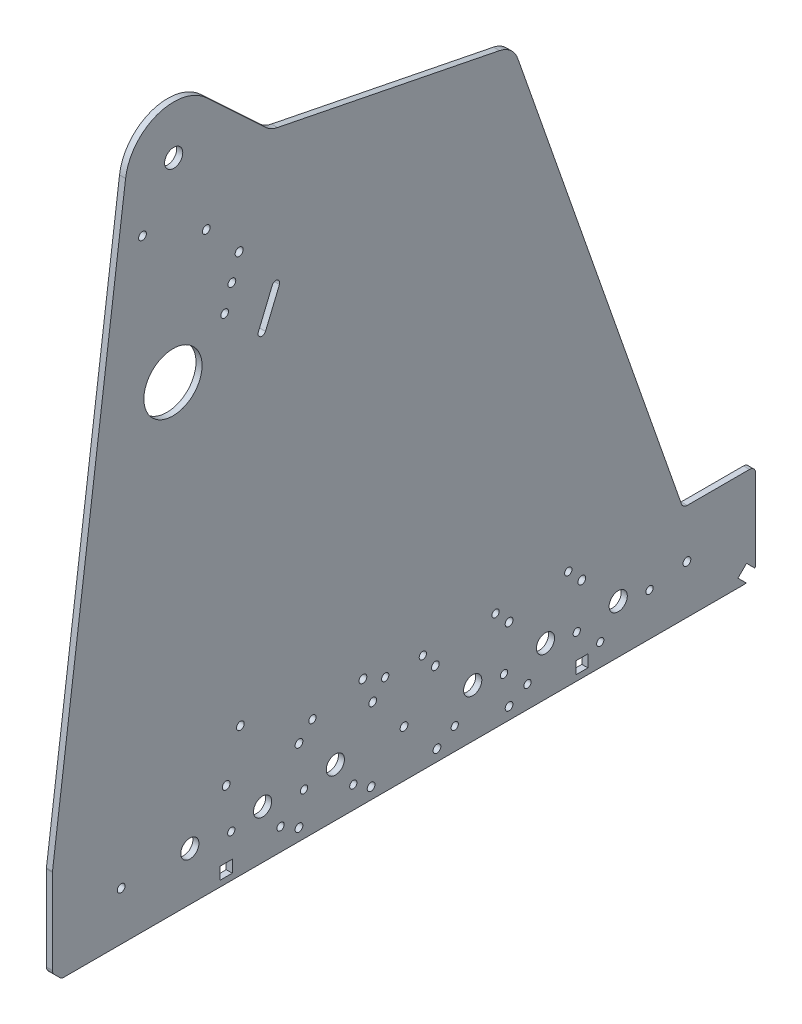
SolidWorks part; units mm, degrees
ref_plane "Front Plane" through (0, 0, 0) normal (0, 0, 1) x (1, 0, 0)
ref_plane "Top Plane" through (0, 0, 0) normal (0, 1, 0) x (1, 0, 0)
ref_plane "Right Plane" through (0, 0, 0) normal (1, 0, 0) x (0, 0, -1)
sketch "Sketch1" plane through (0, 0, 0) normal (1, 0, 0) x (0, 0, -1)
  line L0 (-184.15, -24.6062) -> (184.15, -24.6062)
  line L1 (184.15, -24.6062) -> (184.15, 26.1938)
  line L2 (184.15, 26.1938) -> (146.05, 26.1937)
  line L3 (146.05, 26.1937) -> (57.15, 280.1938)
  line L5 (-145.839, 321.5609) -> (-184.15, 26.1938)
  line L6 (-184.15, 26.1938) -> (-184.15, -24.6062)
  line L7 (-184.15, 350.0437) -> (184.15, 350.0437) construction
  line L8 (57.15, 280.1938) -> (-69.85, 305.5938)
  line L9 (-69.85, 305.5938) -> (-103.3099, 336.854)
  arc A0 (-103.3099, 336.854) -> (-145.839, 321.5609) centre (-120.65, 318.2937) ccw
  point P8 (0, -24.6062)
  dimension "D1" = 368.3
  dimension "D7" = 25.4
  dimension "D2" = 50.8
  dimension "D3" = 38.1
  dimension "D4" = 24.6062
  dimension "D5" = 374.65
  dimension "D6" = 304.8
  dimension "D8" = 342.9
  dimension "D9" = 127
  dimension "D10" = 304.8
  dimension "D11" = 25.4
  dimension "D12" = 127
extrude "Boss-Extrude1" add sketch "Sketch1" along normal blind 3.175
chamfer "Chamfer1" distance 4.7625 angle 45 2 edges at (1.5875, -24.6062, 184.15) (1.5875, -24.6062, -184.15)
fillet "Fillet1" radius 12.7 2 edges at (1.5875, 305.5938, 69.85) (1.5875, 280.1938, -57.15)
fillet "Fillet2" radius 3.175 3 edges at (1.5875, 26.1938, 184.15) (1.5875, 26.1938, -184.15) (1.5875, 26.1937, -146.05)
fillet "Fillet3" radius 3.175 4 edges at (1.5875, -19.8438, -184.15) (1.5875, -24.6062, -179.3875) (1.5875, -19.8437, 184.15) (1.5875, -24.6062, 179.3875)
sketch "Sketch16" plane through (3.175, 0, 0) normal (1, 0, 0) x (0, 0, -1)
  circle A0 centre (112.1746, 0.7937) radius 4.7625
  circle A1 centre (74.0746, 0.7937) radius 4.7625
  circle A2 centre (35.9746, 0.7937) radius 4.7625
  circle A3 centre (-35.9746, 0.7938) radius 4.7625
  circle A4 centre (-74.0746, 0.7938) radius 4.7625
  circle A5 centre (-112.1746, 0.7937) radius 4.7625
  dimension "D1" = 9.525
  dimension "D2" = 9.525
extrude "Cut-Extrude1" cut sketch "Sketch16" against normal up to next
sketch "Sketch25" plane through (3.175, 0, 0) normal (1, 0, 0) x (0, 0, -1)
  circle A0 centre (102.7672, -13.0003) radius 1.905 construction
  circle A1 centre (86.0486, 27.3622) radius 1.905 construction
  circle A2 centre (128.5804, -2.3081) radius 1.905 construction
  circle A3 centre (102.7672, -13.0003) radius 1.905
  circle A4 centre (86.0486, 27.3622) radius 1.905
  circle A5 centre (128.5804, -2.3081) radius 1.905
  circle A6 centre (64.6672, -13.0003) radius 1.905 construction
  circle A8 centre (-9.8486, 27.3622) radius 1.905 construction
  circle A10 centre (-47.9486, 27.3622) radius 1.905 construction
  circle A11 centre (-90.4804, -2.3081) radius 1.905 construction
  circle A12 centre (-64.6672, -13.0003) radius 1.905 construction
  circle A14 centre (-52.3804, -2.3081) radius 1.905 construction
  circle A15 centre (-26.5672, -13.0003) radius 1.905 construction
  circle A16 centre (9.8486, 27.3622) radius 1.905 construction
  circle A17 centre (26.5672, -13.0003) radius 1.905 construction
  circle A18 centre (47.9486, 27.3622) radius 1.905 construction
  circle A19 centre (52.3804, -2.3081) radius 1.905 construction
  circle A20 centre (90.4804, -2.3081) radius 1.905 construction
  circle A21 centre (-9.8486, 27.3622) radius 1.905
  circle A23 centre (-47.9486, 27.3622) radius 1.905
  circle A24 centre (-90.4804, -2.3081) radius 1.905
  circle A25 centre (-64.6672, -13.0003) radius 1.905
  circle A27 centre (-52.3804, -2.3081) radius 1.905
  circle A28 centre (-26.5672, -13.0003) radius 1.905
  circle A29 centre (9.8486, 27.3622) radius 1.905
  circle A30 centre (26.5672, -13.0003) radius 1.905
  circle A31 centre (47.9486, 27.3622) radius 1.905
  circle A32 centre (64.6672, -13.0003) radius 1.905
  circle A33 centre (52.3804, -2.3081) radius 1.905
  circle A34 centre (90.4804, -2.3081) radius 1.905
extrude "Cut-Extrude4" cut sketch "Sketch25" against normal up to next
sketch "Sketch23" plane through (3.175, 0, 0) normal (1, 0, 0) x (0, 0, -1)
  point P0 (-55.0246, -18.3223)
  point P3 (-55.0246, 19.9098)
  point P6 (-93.1246, 19.9098)
  point P9 (-17.2515, -18.6426)
  point P12 (-16.4124, 19.3854)
  point P15 (16.4124, 19.3854)
  point P18 (17.2515, -18.6426)
  point P21 (55.0246, -18.3223)
  point P27 (93.1246, 19.9098)
  point P30 (55.0246, 19.9098)
hole_wizard "#8 (0.16) Diameter Hole1" positions "Sketch23" profile "Sketch24" hole size "#8" standard "ANSI Inch" end condition up to next
sketch "Sketch24" plane through (3.175, -18.3223, 55.0246) normal (0, 1, 0) x (0, 0, -1)
  line L0 (0, 0) -> (0, 3.175)
  line L1 (0, 3.175) -> (2.032, 3.175)
  line L2 (2.032, 3.175) -> (2.032, 0)
  line L5 (2.032, 0) -> (0, 0)
  line L11 (0, -6.35) -> (0, 107.95) construction
  dimension "Thru Hole Dia." = 4.064
  dimension "Thru Hole Depth" = 3.175
sketch "Sketch22" plane through (3.175, 0, 0) normal (1, 0, 0) x (0, 0, -1)
  line L0 (-96.2996, -15.1473) -> (-89.9496, -15.1473) construction
  line L1 (-96.2996, -15.1473) -> (-89.9496, -15.1473)
  line L2 (-96.2996, -15.1473) -> (-96.2996, -21.4973)
  line L3 (-96.2996, -21.4973) -> (-89.9496, -21.4973)
  line L4 (-89.9496, -15.1473) -> (-89.9496, -21.4973)
  line L5 (-96.2996, -15.1473) -> (-89.9496, -21.4973) construction
  line L6 (-96.2996, -21.4973) -> (-89.9496, -15.1473) construction
  line L7 (-89.9496, -15.1473) -> (-89.9496, -19.8734) construction
  line L77 (179.3875, -24.6062) -> (183.8776, -20.1161)
  line L78 (179.3875, -24.6062) -> (174.8974, -20.1161)
  line L79 (183.8776, -20.1161) -> (179.3875, -15.626)
  line L80 (174.8974, -20.1161) -> (179.3875, -15.626)
  line L81 (180.3174, -23.6763) -> (183.2201, -20.7737) construction
  line L82 (-178.0724, -24.6062) -> (178.0724, -24.6062) construction
  line L84 (89.9496, -21.4973) -> (96.2996, -21.4973)
  line L85 (89.9496, -21.4973) -> (89.9496, -15.1473)
  line L86 (89.9496, -15.1473) -> (96.2996, -15.1473)
  line L87 (96.2996, -21.4973) -> (96.2996, -15.1473)
  line L88 (89.9496, -21.4973) -> (96.2996, -15.1473) construction
  line L89 (89.9496, -15.1473) -> (96.2996, -21.4973) construction
  point P0 (-93.1246, -18.3223)
  point P19 (93.1246, -18.3223)
  dimension "D1" = 6.35
  dimension "D2" = 6.35
extrude "Cut-Extrude3" cut sketch "Sketch22" against normal up to next
sketch "Sketch21" plane through (3.175, 0, 0) normal (1, 0, 0) x (0, 0, -1)
  circle A0 centre (-148.1579, 0.7937) radius 2.032
  circle A2 centre (0, 0) radius 2.032
  circle A3 centre (148.1579, 0.7938) radius 2.032
  dimension "D1" = 4.064
extrude "Cut-Extrude2" cut sketch "Sketch21" against normal up to next
sketch "Sketch26" plane through (3.175, 0, 0) normal (1, 0, 0) x (0, 0, -1)
  line L0 (-145.839, 321.5609) -> (-184.1236, 26.3971) construction
  line L1 (-178.0724, -24.6062) -> (178.0724, -24.6062) construction
  circle A0 centre (-121.0218, 216.6937) radius 15.24
  dimension "D1" = 30.48
  dimension "D2" = 38.1
  dimension "D3" = 241.3
extrude "Cut-Extrude5" cut sketch "Sketch26" against normal through all
sketch "Sketch27" plane through (3.175, 0, 0) normal (1, 0, 0) x (0, 0, -1)
  circle A0 centre (-120.65, 318.2937) radius 4.7625
  dimension "D1" = 9.525
extrude "Cut-Extrude6" cut sketch "Sketch27" against normal through all
sketch "Sketch28" plane through (3.175, 0, 0) normal (1, 0, 0) x (0, 0, -1)
  line L0 (-120.65, 318.2937) -> (-103.5612, 277.2599) construction
  line L1 (-103.5612, 277.2599) -> (-86.3654, 258.566) construction
  line L2 (-86.3654, 258.566) -> (-90.1612, 246.4465) construction
  line L3 (-90.1612, 246.4465) -> (-93.9569, 234.327) construction
  line L4 (-145.839, 321.5609) -> (-184.1236, 26.3971) construction
  circle A0 centre (-93.9569, 234.327) radius 2.032
  circle A1 centre (-90.1612, 246.4465) radius 2.032
  circle A2 centre (-86.3654, 258.566) radius 2.0955
  circle A3 centre (-103.5612, 277.2599) radius 2.032
  dimension "D4" = 4.064
  dimension "D5" = 4.191
  dimension "D6" = 4.064
  dimension "D1" = 25.4
  dimension "D2" = 44.45
  dimension "D3" = 12.7
  dimension "D7" = 30
  dimension "D8" = 120
  dimension "D9" = 160
extrude "Cut-Extrude7" cut sketch "Sketch28" against normal through all
sketch "Sketch29" plane through (3.175, 0, 0) normal (1, 0, 0) x (0, 0, -1)
  line L0 (-145.839, 321.5609) -> (-184.1236, 26.3971) construction
  line L1 (-67.1375, 233.9197) -> (-74.4276, 216.3198) construction
  line L2 (-65.2602, 233.1421) -> (-72.5503, 215.5422)
  line L3 (-69.0148, 234.6973) -> (-76.305, 217.0974)
  line L4 (-67.1375, 233.9197) -> (-67.1375, 253.7354) construction
  circle A0 centre (-136.9875, 291.0697) radius 2.032
  circle A2 centre (-120.65, 318.2937) radius 4.7625 construction
  arc A4 (-65.2602, 233.1421) -> (-69.0148, 234.6973) centre (-67.1375, 233.9197) ccw
  arc A5 (-76.305, 217.0974) -> (-72.5503, 215.5422) centre (-74.4276, 216.3198) ccw
  point P8 (-70.7826, 225.1198)
  dimension "D1" = 31.75
  dimension "D2" = 4.064
  dimension "D3" = 69.85
  dimension "D4" = 12.7
  dimension "D5" = 57.15
  dimension "D6" = 19.05
  dimension "D7" = 22.5
extrude "Cut-Extrude8" cut sketch "Sketch29" against normal through all
sketch "Sketch30" plane through (3.175, 0, 0) normal (1, 0, 0) x (0, 0, -1)
  line L0 (-85.7125, 43.2475) -> (-21.5354, 32.3996) construction
  circle A1 centre (-21.5354, 32.3996) radius 7.9375 construction
  circle A2 centre (-85.7125, 43.2475) radius 2.032
  circle A3 centre (-35.9746, 0.7938) radius 4.7625 construction
  circle A4 centre (-48.1454, 36.8975) radius 19.05 construction
  circle A5 centre (-85.7125, 43.2475) radius 19.05 construction
  circle A6 centre (-21.5354, 32.3996) radius 2.032
  circle A7 centre (-74.0746, 0.7938) radius 4.7625 construction
  point P2 (-49.7644, 36.3107)
  point P4 (-48.1454, 36.8975)
  dimension "D2" = 38.1
  dimension "D4" = 15.875
  dimension "D5" = 4.064
  dimension "D6" = 44.45
  dimension "D1" = 38.1
  dimension "D3" = 6.35
extrude "Cut-Extrude9" cut sketch "Sketch30" against normal through all
